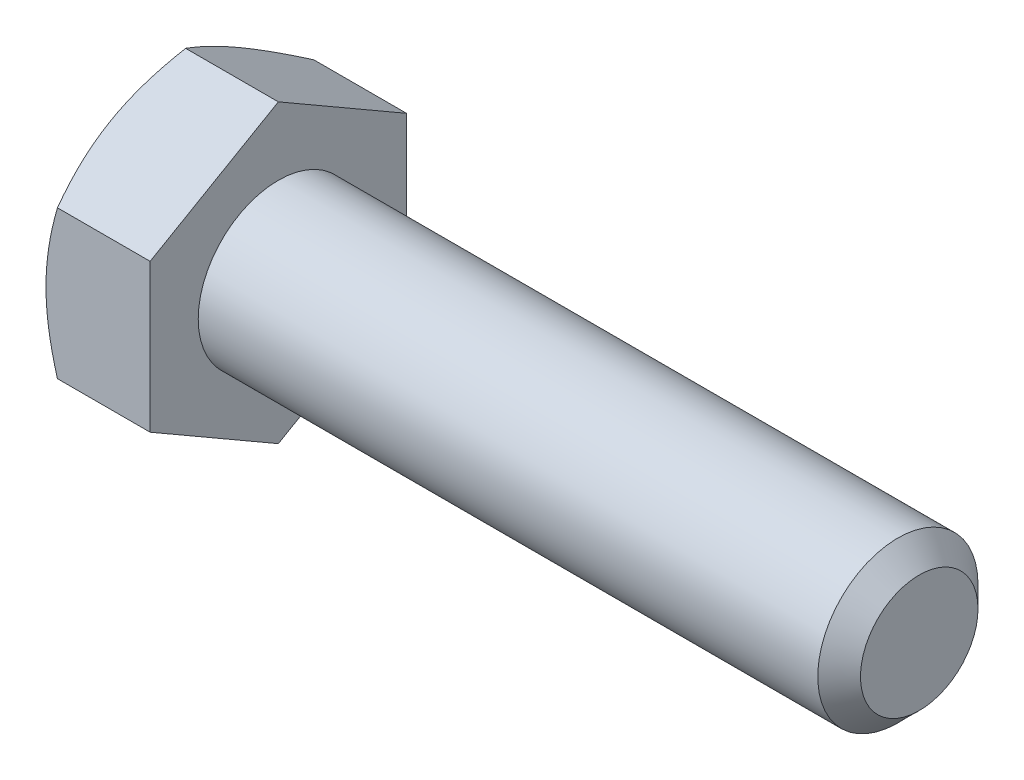
SolidWorks part; units mm, degrees
ref_plane "Front Plane" through (0, 0, 0) normal (0, 0, 1) x (1, 0, 0)
ref_plane "Top Plane" through (0, 0, 0) normal (0, 1, 0) x (1, 0, 0)
ref_plane "Right Plane" through (0, 0, 0) normal (1, 0, 0) x (0, 0, -1)
sketch "Sketch1" plane through (0, 0, 0) normal (0, 0, 1) x (1, 0, 0)
  line L0 (-18.4547, 0) -> (18.4547, 0) construction
  line L1 (18.4547, 3.9688) -> (18.4547, -3.9688) construction
  line L2 (-13.2953, 6.35) -> (-13.2953, -6.35) construction
  line L3 (-18.4547, 6.35) -> (-18.4547, -6.35) construction
  line L4 (18.4547, 3.9688) -> (19.8658, 3.9688) construction
  point P9 (-13.2953, 0)
  point P10 (13.5158, -3.9688)
  dimension "Screw Dia" = 7.9375
  dimension "Hex" = 12.7
  dimension "Head Ht" = 5.1594
  dimension "Screw Lenght" = 31.75
  dimension "D1" = 4.9389
  dimension "Pitch" = 1.4111
ref_plane "Plane4" through (-13.2953, 0, 0) normal (1, 0, 0) x (0, 0, -1)
sketch "Sketch14" plane through (-13.2953, 0, 0) normal (1, 0, 0) x (0, 0, -1)
  line L1 (0, -7.3323) -> (6.35, -3.6662) construction
  line L2 (6.35, -3.6662) -> (6.35, 3.6662) construction
  line L3 (6.35, 3.6662) -> (0, 7.3323) construction
  line L4 (0, 7.3323) -> (-6.35, 3.6662) construction
  line L5 (-6.35, 3.6662) -> (-6.35, -3.6662) construction
  line L6 (-6.35, -3.6662) -> (0, -7.3323) construction
  circle A0 centre (0, 0) radius 6.35 construction
ref_plane "Plane2" through (18.4547, 0, 0) normal (1, 0, 0) x (0, 0, -1)
sketch "Sketch5" plane through (18.4547, 0, 0) normal (1, 0, 0) x (0, 0, -1)
  circle A0 centre (0, 0) radius 3.9688
extrude "Boss-Extrude3" add sketch "Sketch5" against normal up to vertex (31.75 mm away) up to point (-13.2953, 0, 0)
sketch "Sketch9" [suppressed] plane through (18.4547, 0, 0) normal (1, 0, 0) x (0, 0, -1)
  circle A1 centre (0, 0) radius 3.9688
  circle A2 centre (0, 0) radius 3.9688
  dimension "D1" = 0
chamfer "Chamfer1" distance 1.0583 angle 45 1 edges at (18.4547, 0, -3.9688)
sketch "Sketch6" plane through (-13.2953, 0, 0) normal (-1, 0, 0) x (0, 0, 1)
  line L0 (0, 6.35) -> (0, -6.35) construction
  line L1 (6.35, 3.6662) -> (0, 7.3323)
  line L2 (0, 7.3323) -> (-6.35, 3.6662)
  line L3 (-6.35, 3.6662) -> (-6.35, -3.6662)
  line L4 (-6.35, -3.6662) -> (0, -7.3323)
  line L5 (0, -7.3323) -> (6.35, -3.6662)
  line L6 (6.35, -3.6662) -> (6.35, 3.6662)
  circle A0 centre (0, 0) radius 6.35 construction
extrude "Boss-Extrude4" add sketch "Sketch6" along normal up to vertex (5.1594 mm away) up to point (-18.4547, -6.35, 0)
sketch "Sketch8" plane through (-18.4547, 0, 0) normal (-1, 0, 0) x (0, 0, 1)
  circle A0 centre (0, 0) radius 6.35 construction
  circle A1 centre (0, 0) radius 6.35
extrude "Cut-Extrude3" cut sketch "Sketch8" against normal through all draft 60 flip side to cut
split "Split1" [suppressed] bodies to split 113
curve "Helix/Spiral1" [suppressed] pitch 1.4111 height 33.1611 turns 23.5 parameters "Pitch"=1.4111
sketch "Sketch10" [suppressed] plane through (0, 0, 0) normal (0, 0, 1) x (1, 0, 0)
  line L0 (18.4547, 3.9688) -> (18.9839, 3.0522)
  line L1 (18.9839, 3.0522) -> (19.1602, 3.0522)
  line L2 (19.1602, 3.0522) -> (19.6894, 3.9688)
  line L3 (18.4547, 3.9688) -> (19.6894, 3.9688)
  line L4 (19.072, 3.9688) -> (19.072, 3.0522) construction
  line L5 (18.7193, 3.5105) -> (19.4248, 3.5105) construction
  dimension "D1" = 60
  dimension "D2" = 0.1764
  dimension "D3" = 0.7056
sweep "Cut-Sweep1" [suppressed] cut profiles "Sketch10" path "Helix/Spiral1"
sketch "Sketch13" [suppressed] plane through (-13.2953, 0, 0) normal (1, 0, 0) x (0, 0, -1)
  circle A0 centre (0, 0) radius 3.9688
extrude "Boss-Extrude5" [suppressed] add sketch "Sketch13" along normal blind 2.54 draft 30
sketch "Sketch12" plane through (-18.4547, 0, 0) normal (-1, 0, 0) x (0, 0, 1)
  line L0 (0, 4.8895) -> (0, 2.7305) construction
  line L1 (0.1905, 4.8895) -> (0.1905, 2.7305)
  line L2 (-0.1905, 4.8895) -> (-0.1905, 2.7305)
  line L3 (0, 3.9688) -> (0, -3.9688) construction
  arc A0 (0.1905, 4.8895) -> (-0.1905, 4.8895) centre (0, 4.8895) ccw
  arc A1 (-0.1905, 2.7305) -> (0.1905, 2.7305) centre (0, 2.7305) ccw
  circle A3 centre (0, 0) radius 2.54 construction
  circle A4 centre (0, 0) radius 5.08 construction
  point P2 (0, 3.81)
  dimension "D1" = 5.08
  dimension "D3" = 10.16
  dimension "D2" = 0.381
extrude "Cut-Extrude4" cut sketch "Sketch12" against normal blind 0.254
pattern_circular "CirPattern1" count 6 over 360 about axis through (-13.2953, 0, 0) along (1, 0, 0) of "Cut-Extrude4"
equation "\"D2@Sketch10\" = \"Pitch@Sketch1\" * .125"
equation "\"D3@Sketch10\" = \"Pitch@Sketch1\" * .5"
equation "\"D3@Helix/Spiral1\" = \"Screw Lenght@Sketch1\" + \"Pitch@Sketch1\""
equation "\"D1@Chamfer1\" = \"Pitch@Sketch1\" * .75"
equation "\"D1@Sketch12\" = \"Hex@Sketch1\"*.4"
equation "\"D3@Sketch12\" = \"Hex@Sketch1\"*.8"
equation "\"D2@Sketch12\" = \"Hex@Sketch1\"*.03"
equation "\"D1@Sketch1\" = \"Pitch@Sketch1\" * 3.5"
equation "\"Pitch@Helix/Spiral1\"=\"Pitch@Sketch1\""
